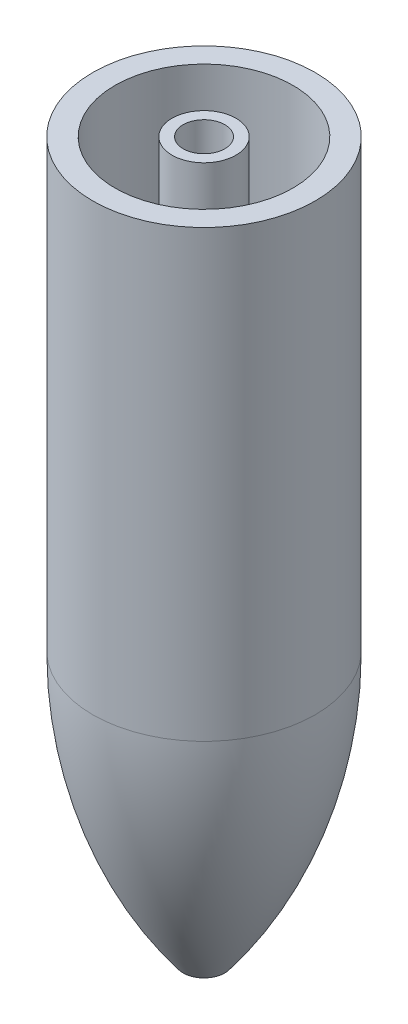
SolidWorks part; units mm, degrees
ref_plane "Front" through (0, 0, 0) normal (0, 0, 1) x (1, 0, 0)
ref_plane "Top" through (0, 0, 0) normal (0, 1, 0) x (1, 0, 0)
ref_plane "Right" through (0, 0, 0) normal (1, 0, 0) x (0, 0, -1)
ref_axis "Center Axis" through (0, 0, -13.97) along (0, 0, 1)
sketch "Sketch1" plane through (0, 0, 0) normal (0, 0, 1) x (1, 0, 0)
  line L0 (0, 0) -> (0, -50.8)
  line L1 (12.7, -84.401) -> (12.7, 0)
  line L2 (12.7, 0) -> (0, 0)
  arc A0 (0, -50.8) -> (12.7, -84.401) centre (50.8, -50.8) ccw
  dimension "D4" = 50.8
  dimension "D1" = 12.7
  dimension "D3" = 50.8
revolve "Revolve1" add sketch "Sketch1" angle 360 about L1
sketch "Sketch2" plane through (0, 0, 0) normal (0, 1, 0) x (1, 0, 0)
  circle A0 centre (12.7, 0) radius 2.3813
  dimension "D1" = 4.7625
extrude "Cut-Extrude1" cut sketch "Sketch2" against normal through all
sketch "Sketch5" plane through (0, 0, 0) normal (0, 1, 0) x (1, 0, 0)
  circle A0 centre (12.7, 0) radius 3.6512
  circle A1 centre (12.7, 0) radius 2.3812
  circle A2 centre (12.7, 0) radius 2.3813
  circle A5 centre (12.7, 0) radius 10.16
  circle A6 centre (12.7, 0) radius 10.16
  dimension "D1" = 0
  dimension "D2" = 1.27
  dimension "D3" = 2.54
extrude "Cut-Extrude4" cut sketch "Sketch5" against normal blind 50.8 contours A6 A0 region at (2.8274, 0, 0)
